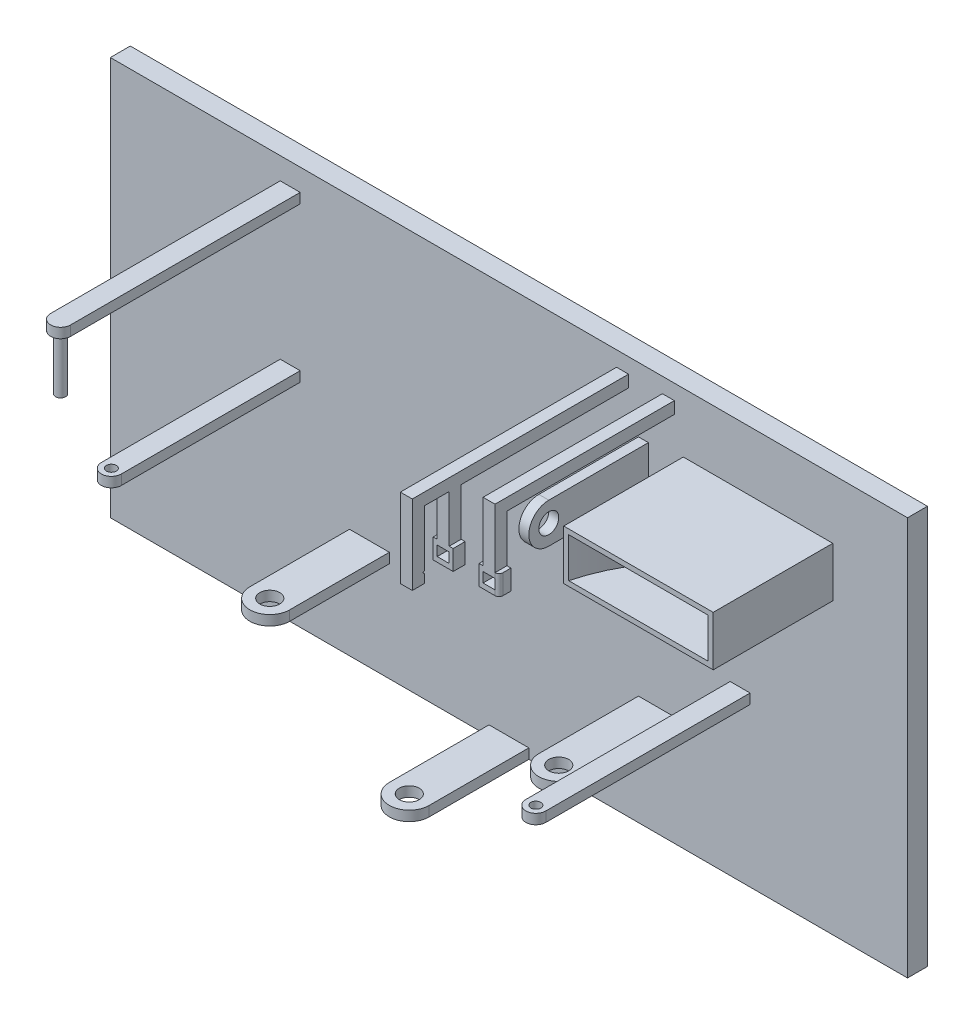
SolidWorks part; units mm, degrees
ref_plane "前视基准面" through (0, 0, 0) normal (0, 0, 1) x (1, 0, 0)
ref_plane "上视基准面" through (0, 0, 0) normal (0, 1, 0) x (1, 0, 0)
ref_plane "右视基准面" through (0, 0, 0) normal (1, 0, 0) x (0, 0, -1)
sketch "草图1" plane through (0, 0, 0) normal (0, 0, 1) x (1, 0, 0)
  line L1 (-400, -200) -> (400, -200)
  line L2 (-400, -200) -> (-400, 200)
  line L3 (-400, 200) -> (400, 200)
  line L4 (400, -200) -> (400, 200)
  line L5 (-400, -200) -> (400, 200) construction
  line L6 (-400, 200) -> (400, -200) construction
  point P0 (0, 0)
  dimension "D1" = 400
  dimension "D2" = 800
extrude "凸台-拉伸1" add sketch "草图1" along normal blind 20
sketch "草图2" plane through (0, 0, 20) normal (0, 0, 1) x (1, 0, 0)
  line L0 (0, 0) -> (-257.383, 0) construction
  line L1 (0, 0) -> (0, 146.9205) construction
  line L2 (-400, -200) -> (400, -200) construction
  line L3 (-20, -200) -> (20, -200)
  line L4 (-20, -200) -> (-20, -190)
  line L5 (-20, -190) -> (20, -190)
  line L6 (20, -200) -> (20, -190)
  line L7 (-20, -200) -> (20, -190) construction
  line L8 (-20, -190) -> (20, -200) construction
  point P2 (0, -195)
  point P4 (0, -195)
  dimension "D1" = 10
  dimension "D2" = 40
extrude "凸台-拉伸2" add sketch "草图2" along normal blind 100
sketch "草图3" plane through (0, -200, 0) normal (0, -1, 0) x (1, 0, 0)
  line L0 (-20, 120) -> (20, 120) construction
  circle A0 centre (0, 120) radius 20
extrude "凸台-拉伸3" add sketch "草图3" against normal blind 10
sketch "草图4" plane through (0, -200, 0) normal (0, -1, 0) x (1, 0, 0)
  circle A0 centre (0, 120) radius 10
  dimension "D1" = 20
extrude "切除-拉伸1" cut sketch "草图4" against normal blind 10
sketch "草图5" plane through (0, 0, 20) normal (0, 0, 1) x (1, 0, 0)
  line L0 (20, -200) -> (400, -200) construction
  line L1 (130, -90) -> (170, -90)
  line L2 (130, -90) -> (130, -100)
  line L3 (130, -100) -> (170, -100)
  line L4 (170, -90) -> (170, -100)
  line L5 (-20, -190) -> (-20, -200) construction
  dimension "D1" = 10
  dimension "D2" = 40
  dimension "D3" = 100
  dimension "D4" = 150
extrude "凸台-拉伸4" add sketch "草图5" along normal blind 100
sketch "草图6" plane through (0, -100, 0) normal (0, -1, 0) x (1, 0, 0)
  line L0 (130, 120) -> (170, 120) construction
  circle A0 centre (150, 120) radius 20
  circle A1 centre (150, 120) radius 10
  dimension "D1" = 20
extrude "凸台-拉伸5" add sketch "草图6" against normal blind 10
sketch "草图8" plane through (0, -100, 0) normal (0, -1, 0) x (1, 0, 0)
  line L0 (140, 120) -> (160, 120) construction
  circle A0 centre (150, 120) radius 10
extrude "切除-拉伸2" cut sketch "草图8" against normal blind 10
sketch "草图9" plane through (0, 0, 20) normal (0, 0, 1) x (1, 0, 0)
  line L0 (20, -190) -> (-20, -190) construction
  line L1 (130, 135.3) -> (140, 135.3)
  line L2 (130, 135.3) -> (130, 95.3)
  line L3 (130, 95.3) -> (140, 95.3)
  line L4 (140, 135.3) -> (140, 95.3)
  line L6 (130, -90) -> (130, -100) construction
  dimension "D1" = 40
  dimension "D2" = 10
  dimension "D3" = 285.3
  dimension "D4" = 0
extrude "凸台-拉伸6" add sketch "草图9" along normal blind 100
sketch "草图10" plane through (140, 0, 0) normal (1, 0, 0) x (0, 0, -1)
  line L0 (-120, 95.3) -> (-120, 135.3) construction
  circle A0 centre (-120, 115.3) radius 20
extrude "凸台-拉伸7" add sketch "草图10" against normal blind 10
sketch "草图11" plane through (140, 0, 0) normal (1, 0, 0) x (0, 0, -1)
  circle A0 centre (-120, 115.3) radius 10
  dimension "D1" = 20
extrude "切除-拉伸3" cut sketch "草图11" against normal blind 10
sketch "草图12" plane through (0, 0, 20) normal (0, 0, 1) x (1, 0, 0)
  line L0 (170, -90) -> (130, -90) construction
  line L1 (-160, -90) -> (-120, -90)
  line L2 (-160, -90) -> (-160, -100)
  line L3 (-160, -100) -> (-120, -100)
  line L4 (-120, -90) -> (-120, -100)
  line L6 (-20, -190) -> (-20, -200) construction
  dimension "D1" = 10
  dimension "D2" = 40
  dimension "D3" = 100
extrude "凸台-拉伸8" add sketch "草图12" along normal blind 100
sketch "草图13" plane through (0, -100, 0) normal (0, -1, 0) x (1, 0, 0)
  line L0 (-160, 120) -> (-120, 120) construction
  circle A0 centre (-140, 120) radius 20
extrude "凸台-拉伸9" add sketch "草图13" against normal blind 10
sketch "草图14" plane through (0, -100, 0) normal (0, -1, 0) x (1, 0, 0)
  circle A0 centre (-140, 120) radius 10
  dimension "D1" = 20
extrude "切除-拉伸4" cut sketch "草图14" against normal blind 10
sketch "草图15" plane through (0, 0, 20) normal (0, 0, 1) x (1, 0, 0)
  line L1 (-229.5, 23.0397) -> (-209.5, 23.0397)
  line L2 (-229.5, 23.0397) -> (-229.5, 13.0397)
  line L3 (-229.5, 13.0397) -> (-209.5, 13.0397)
  line L4 (-209.5, 23.0397) -> (-209.5, 13.0397)
  line L5 (-229.5, 23.0397) -> (-209.5, 13.0397) construction
  line L6 (-229.5, 13.0397) -> (-209.5, 23.0397) construction
  line L7 (-160, -90) -> (-160, -100) construction
  point P0 (-219.5, 18.0397)
  dimension "D1" = 10
  dimension "D2" = 20
  dimension "D3" = 59.5
extrude "凸台-拉伸10" add sketch "草图15" along normal blind 179.5
sketch "草图16" plane through (0, 13.0397, 0) normal (0, -1, 0) x (1, 0, 0)
  line L0 (-229.5, 199.5) -> (-209.5, 199.5) construction
  circle A0 centre (-219.5, 199.5) radius 10
extrude "凸台-拉伸11" add sketch "草图16" against normal blind 10
sketch "草图17" plane through (0, 13.0397, 0) normal (0, -1, 0) x (1, 0, 0)
  circle A0 centre (-219.5, 199.5) radius 4.97
  dimension "D1" = 9.94
extrude "切除-拉伸5" cut sketch "草图17" against normal blind 10
sketch "草图18" plane through (0, 0, 20) normal (0, 0, 1) x (1, 0, 0)
  line L1 (120.03, 172.8211) -> (108.03, 172.8211)
  line L2 (120.03, 172.8211) -> (120.03, 184.8211)
  line L3 (120.03, 184.8211) -> (108.03, 184.8211)
  line L4 (108.03, 172.8211) -> (108.03, 184.8211)
  line L6 (130, 135.3) -> (130, 95.3) construction
  dimension "D1" = 12
  dimension "D2" = 9.97
extrude "凸台-拉伸12" add sketch "草图18" along normal blind 180
sketch "草图19" plane through (0, 172.8211, 0) normal (0, -1, 0) x (1, 0, 0)
  line L5 (108.03, 200) -> (108.03, 20) construction
  line L6 (108.03, 200) -> (120.03, 200)
  line L7 (108.03, 200) -> (108.03, 188)
  line L8 (108.03, 188) -> (120.03, 188)
  line L9 (120.03, 200) -> (120.03, 188)
  line L10 (120.03, 200) -> (120.03, 20) construction
  line L11 (108.03, 200) -> (120.03, 200) construction
  dimension "D1" = 12
extrude "凸台-拉伸13" add sketch "草图19" along normal blind 57.52
sketch "草图20" plane through (0, 0, 200) normal (0, 0, 1) x (1, 0, 0)
  line L0 (120.03, 115.3011) -> (108.03, 115.3011) construction
  line L1 (104.03, 105.3011) -> (124.03, 105.3011)
  line L2 (104.03, 105.3011) -> (104.03, 125.3011)
  line L3 (104.03, 125.3011) -> (124.03, 125.3011)
  line L4 (124.03, 105.3011) -> (124.03, 125.3011)
  line L5 (104.03, 105.3011) -> (124.03, 125.3011) construction
  line L6 (104.03, 125.3011) -> (124.03, 105.3011) construction
  point P0 (114.03, 115.3011)
  dimension "D1" = 20
extrude "凸台-拉伸14" add sketch "草图20" against normal blind 12
sketch "草图21" plane through (0, 0, 200) normal (0, 0, 1) x (1, 0, 0)
  line L0 (124.03, 115.3011) -> (104.03, 115.3011)
  line L1 (124.03, 105.3011) -> (124.03, 125.3011) construction
  line L2 (104.03, 125.3011) -> (104.03, 105.3011) construction
  line L3 (114.03, 105.3011) -> (114.03, 115.3011)
  line L4 (104.03, 105.3011) -> (124.03, 105.3011) construction
  line L6 (108.03, 110.3011) -> (120.03, 110.3011)
  line L7 (108.03, 110.3011) -> (108.03, 120.3011)
  line L8 (108.03, 120.3011) -> (120.03, 120.3011)
  line L9 (120.03, 110.3011) -> (120.03, 120.3011)
  line L10 (108.03, 110.3011) -> (120.03, 120.3011) construction
  line L11 (108.03, 120.3011) -> (120.03, 110.3011) construction
  dimension "D1" = 10
  dimension "D2" = 12
extrude "切除-拉伸6" cut sketch "草图21" against normal blind 12 contours L7 L6 L3 L0 | L0 L9 L8 L7 | L6 L9 L0 L3 region at (117.03, 112.8011, 200) region at (114.03, 117.8011, 200) region at (111.03, 112.8011, 200)
sketch "草图23" plane through (0, 0, 20) normal (0, 0, 1) x (1, 0, 0)
  line L0 (120.03, 184.8211) -> (108.03, 184.8211) construction
  line L1 (154.03, 184.8211) -> (166.03, 184.8211)
  line L2 (154.03, 184.8211) -> (154.03, 172.8211)
  line L3 (154.03, 172.8211) -> (166.03, 172.8211)
  line L4 (166.03, 184.8211) -> (166.03, 172.8211)
  line L6 (120.03, 125.3011) -> (120.03, 184.8211) construction
  dimension "D1" = 12
  dimension "D2" = 34
extrude "凸台-拉伸15" add sketch "草图23" along normal blind 180
sketch "草图24" plane through (0, 172.8211, 0) normal (0, -1, 0) x (1, 0, 0)
  line L1 (154.03, 200) -> (166.03, 200)
  line L2 (154.03, 200) -> (154.03, 188)
  line L3 (154.03, 188) -> (166.03, 188)
  line L4 (166.03, 200) -> (166.03, 188)
  line L5 (166.03, 200) -> (166.03, 20) construction
  dimension "D1" = 12
extrude "凸台-拉伸16" add sketch "草图24" along normal blind 67.52
sketch "草图25" plane through (0, 0, 200) normal (0, 0, 1) x (1, 0, 0)
  line L0 (160.03, 105.3011) -> (150.03, 105.3011)
  line L1 (166.03, 105.3011) -> (154.03, 105.3011) construction
  line L2 (150.03, 105.3011) -> (150.03, 125.3011)
  line L3 (150.03, 125.3011) -> (170.03, 125.3011)
  line L4 (170.03, 125.3011) -> (170.03, 105.3011)
  line L5 (170.03, 105.3011) -> (160.03, 105.3011)
  dimension "D1" = 10
  dimension "D2" = 20
  dimension "D3" = 20
extrude "凸台-拉伸17" add sketch "草图25" against normal blind 12
sketch "草图26" plane through (0, 0, 200) normal (0, 0, 1) x (1, 0, 0)
  line L0 (170.03, 115.3011) -> (150.03, 115.3011)
  line L1 (170.03, 105.3011) -> (170.03, 125.3011) construction
  line L2 (150.03, 125.3011) -> (150.03, 105.3011) construction
  line L3 (160.03, 105.3011) -> (160.03, 115.3011)
  line L4 (170.03, 105.3011) -> (150.03, 105.3011) construction
  line L6 (154.03, 110.3011) -> (166.03, 110.3011)
  line L7 (154.03, 110.3011) -> (154.03, 120.3011)
  line L8 (154.03, 120.3011) -> (166.03, 120.3011)
  line L9 (166.03, 110.3011) -> (166.03, 120.3011)
  line L10 (154.03, 110.3011) -> (166.03, 120.3011) construction
  line L11 (154.03, 120.3011) -> (166.03, 110.3011) construction
  dimension "D1" = 10
  dimension "D2" = 12
extrude "切除-拉伸7" cut sketch "草图26" against normal blind 24 contours L0 L9 L8 L7 | L7 L6 L3 L0 | L6 L9 L0 L3 region at (163.03, 112.8011, 200) region at (160.03, 117.8011, 200) region at (157.03, 112.8011, 200)
sketch "草图27" plane through (0, 0, 200) normal (0, 0, 1) x (1, 0, 0)
  line L0 (120.03, 125.3011) -> (120.03, 184.8211) construction
  line L1 (108.03, 184.8211) -> (120.03, 184.8211)
  line L2 (108.03, 184.8211) -> (108.03, 172.8211)
  line L3 (108.03, 172.8211) -> (120.03, 172.8211)
  line L4 (120.03, 184.8211) -> (120.03, 172.8211)
  line L5 (120.03, 172.8211) -> (120.03, 184.8211) construction
extrude "凸台-拉伸18" add sketch "草图27" along normal blind 25
sketch "草图28" plane through (0, 184.8211, 0) normal (0, 1, 0) x (1, 0, 0)
  line L1 (108.03, -225) -> (120.03, -225)
  line L2 (108.03, -225) -> (108.03, -237)
  line L3 (108.03, -237) -> (120.03, -237)
  line L4 (120.03, -225) -> (120.03, -237)
  dimension "D1" = 12
extrude "凸台-拉伸19" add sketch "草图28" against normal up to surface (79.52 mm away) up to face at (114.03, 105.3011, 194)
sketch "草图29" plane through (108.03, 0, 0) normal (-1, 0, 0) x (0, 0, 1)
  line L0 (225, 105.3011) -> (225, 172.8211) construction
  line L1 (225, 105.3011) -> (237, 105.3011) construction
  circle A0 centre (225, 115.3011) radius 1.1
  dimension "D1" = 2.2
  dimension "D2" = 10
extrude "切除-拉伸8" cut sketch "草图29" against normal blind 25
sketch "草图30" plane through (0, 0, 20) normal (0, 0, 1) x (1, 0, 0)
  line L0 (166.03, 172.8211) -> (166.03, 184.8211) construction
  line L1 (222.03, -31.2933) -> (242.03, -31.2933)
  line L2 (222.03, -31.2933) -> (222.03, -41.2933)
  line L3 (222.03, -41.2933) -> (242.03, -41.2933)
  line L4 (242.03, -31.2933) -> (242.03, -41.2933)
  dimension "D1" = 10
  dimension "D2" = 20
  dimension "D3" = 56
extrude "凸台-拉伸20" add sketch "草图30" along normal blind 205
sketch "草图31" plane through (0, -41.2933, 0) normal (0, -1, 0) x (1, 0, 0)
  line L0 (222.03, 225) -> (242.03, 225) construction
  circle A0 centre (232.03, 225) radius 10
extrude "凸台-拉伸21" add sketch "草图31" against normal blind 10
sketch "草图32" plane through (0, -41.2933, 0) normal (0, -1, 0) x (1, 0, 0)
  circle A0 centre (232.03, 225) radius 5
  dimension "D1" = 10
extrude "切除-拉伸9" cut sketch "草图32" against normal blind 10
fillet "圆角1" radius 4 1 edges at (170.03, 115.3011, 200)
sketch "草图34" plane through (0, 0, 20) normal (0, 0, 1) x (1, 0, 0)
  line L0 (140, 95.3) -> (140, 135.3) construction
  line L1 (180, 95.3) -> (220, 95.3)
  line L2 (180, 95.3) -> (180, 135.3)
  line L3 (180, 135.3) -> (220, 135.3)
  line L4 (220, 95.3) -> (220, 135.3)
  line L5 (180, 95.3) -> (220, 135.3) construction
  line L6 (180, 135.3) -> (220, 95.3) construction
  line L9 (175, 90.3) -> (225, 90.3)
  line L10 (175, 90.3) -> (175, 140.3)
  line L11 (175, 140.3) -> (225, 140.3)
  line L12 (225, 90.3) -> (225, 140.3)
  line L13 (175, 90.3) -> (225, 140.3) construction
  line L14 (175, 140.3) -> (225, 90.3) construction
  point P0 (200, 115.3)
  point P7 (200, 115.3)
  dimension "D1" = 40
  dimension "D2" = 40
  dimension "D3" = 50
extrude "凸台-拉伸22" add sketch "草图34" along normal blind 120
sketch "草图35" plane through (0, 90.3, 0) normal (0, -1, 0) x (1, 0, 0)
  line L0 (175, 140) -> (175, 20) construction
  line L2 (20, 20) -> (400, 20) construction
  line L3 (175, 140) -> (180, 140)
  line L4 (175, 140) -> (225, 140) construction
  line L5 (180, 140) -> (180, 20)
  line L6 (175, 20) -> (225, 20) construction
  circle A0 centre (334.641, 179.641) radius 159.641
  line M2 (225, 20) -> (225, 140)
  line M3 (225, 140) -> (175, 140)
  dimension "D1" = 5
extrude "切除-拉伸11" cut sketch "草图35" against normal blind 123 contours A0 M2 M3 | A0 M3 M2 region at (338.0305, 90.3, 181.4543) region at (208.2776, 90.3, 112.0395)
sketch "草图36" plane through (0, 0, 20) normal (0, 0, 1) x (1, 0, 0)
  line L1 (225, 140.3) -> (325, 140.3)
  line L2 (225, 140.3) -> (225, 90.3)
  line L3 (225, 90.3) -> (325, 90.3)
  line L4 (325, 140.3) -> (325, 90.3)
  dimension "D1" = 100
extrude "凸台-拉伸23" add sketch "草图36" along normal blind 44
sketch "草图38" plane through (0, 0, 20) normal (0, 0, 1) x (1, 0, 0)
  line L0 (325, 90.3) -> (325, 140.3) construction
  line L1 (180, 140.3) -> (325, 140.3)
  line L2 (180, 140.3) -> (180, 135.3)
  line L3 (180, 135.3) -> (325, 135.3)
  line L4 (325, 140.3) -> (325, 135.3)
  line L6 (180, 95.3) -> (325, 95.3)
  line L7 (180, 95.3) -> (180, 90.3)
  line L8 (180, 90.3) -> (325, 90.3)
  line L9 (325, 95.3) -> (325, 90.3)
  line L10 (180, 135.3) -> (220, 135.3)
  line L11 (180, 135.3) -> (180, 95.3)
  line L12 (180, 95.3) -> (220, 95.3)
  line L13 (220, 135.3) -> (220, 95.3)
  line M1 (180, 95.3) -> (220, 95.3)
  line M2 (220, 95.3) -> (220, 135.3)
  line M3 (220, 135.3) -> (180, 135.3)
  line M4 (180, 135.3) -> (180, 95.3)
  dimension "D1" = 5
extrude "凸台-拉伸24" add sketch "草图38" along normal up to surface (120 mm away) contours M4 M1 M2 M3 region at (200, 115.3, 20) up to face at (178.3333, 115.3, 140)
sketch "草图39" plane through (0, 95.3, 0) normal (0, -1, 0) x (1, 0, 0)
  line L0 (220, 140) -> (220, 68.5433) construction
  line L1 (220, 140) -> (180, 140) construction
  line L2 (220, 140) -> (220, 68.5433)
  line L3 (220, 140) -> (180, 140)
  arc A0 (180, 140) -> (220, 68.5433) centre (334.641, 179.641) ccw construction
  arc A1 (180, 140) -> (220, 68.5433) centre (334.641, 179.641) ccw
extrude "切除-拉伸12" cut sketch "草图39" against normal blind 138
sketch "草图40" plane through (0, 0, 64) normal (0, 0, 1) x (1, 0, 0)
  line L10 (175, 140.3) -> (175, 90.3) construction
  line L11 (325, 140.3) -> (175, 140.3)
  line L12 (325, 140.3) -> (325, 135.3)
  line L13 (325, 135.3) -> (175, 135.3)
  line L14 (175, 140.3) -> (175, 135.3)
  line L16 (325, 140.3) -> (320, 140.3)
  line L17 (325, 140.3) -> (325, 135.3)
  line L18 (325, 90.3) -> (320, 90.3)
  line L20 (225, 90.3) -> (325, 90.3) construction
  line L22 (325, 90.3) -> (175, 90.3)
  line L23 (325, 90.3) -> (325, 95.3)
  line L24 (325, 95.3) -> (175, 95.3)
  line L25 (175, 90.3) -> (175, 95.3)
  line L26 (175, 140.3) -> (175, 90.3) construction
  line L27 (325, 95.3) -> (325, 90.3)
  line L28 (325, 95.3) -> (325, 90.3)
  line M1 (225, 140.3) -> (225, 90.3)
  line M2 (225, 90.3) -> (325, 90.3)
  line M3 (325, 90.3) -> (325, 140.3)
  line M4 (325, 140.3) -> (225, 140.3)
  dimension "D1" = 5
  dimension "D2" = 50
  dimension "D3" = 5
  dimension "D4" = 5
  dimension "D5" = 150
extrude "凸台-拉伸26" add sketch "草图40" along normal up to surface (76 mm away) contours L13 L11 M3 M4 M1 | L24 M3 M1 M2 | L25 L22 L24 M1 | L11 L14 L13 M1 region at (275, 137.8, 64) region at (200, 137.8, 64) region at (275, 92.8, 64) region at (200, 92.8, 64) up to face at (177.5, 115.3, 140)
sketch "草图41" plane through (0, 0, 64) normal (0, 0, 1) x (1, 0, 0)
  line L1 (325, 135.3) -> (320, 135.3)
  line L2 (325, 135.3) -> (325, 95.3)
  line L3 (325, 95.3) -> (320, 95.3)
  line L4 (320, 135.3) -> (320, 95.3)
  line L5 (180, 95.3) -> (325, 95.3) construction
  dimension "D1" = 40
  dimension "D2" = 5
extrude "凸台-拉伸27" add sketch "草图41" along normal up to surface (76 mm away) up to face at (251.25, 115.3, 140)
sketch "草图42" plane through (0, 0, 20) normal (0, 0, 1) x (1, 0, 0)
  line L0 (-209.5, 23.0397) -> (-229.5, 23.0397) construction
  line L1 (-229.5, 178.0397) -> (-209.5, 178.0397)
  line L2 (-229.5, 178.0397) -> (-229.5, 168.0397)
  line L3 (-229.5, 168.0397) -> (-209.5, 168.0397)
  line L4 (-209.5, 178.0397) -> (-209.5, 168.0397)
  line L5 (-229.5, 23.0397) -> (-229.5, 13.0397) construction
  dimension "D1" = 10
  dimension "D2" = 145
  dimension "D3" = 20
extrude "凸台-拉伸28" add sketch "草图42" along normal blind 230.4
sketch "草图43" plane through (0, 178.0397, 0) normal (0, 1, 0) x (1, 0, 0)
  line L0 (-209.5, -250.4) -> (-229.5, -250.4) construction
  circle A0 centre (-219.5, -250.4) radius 10
extrude "凸台-拉伸29" add sketch "草图43" against normal blind 10
sketch "草图44" plane through (0, 178.0397, 0) normal (0, 1, 0) x (1, 0, 0)
  circle A0 centre (-219.5, -250.4) radius 5
  dimension "D1" = 10
extrude "凸台-拉伸30" add sketch "草图44" against normal blind 65
